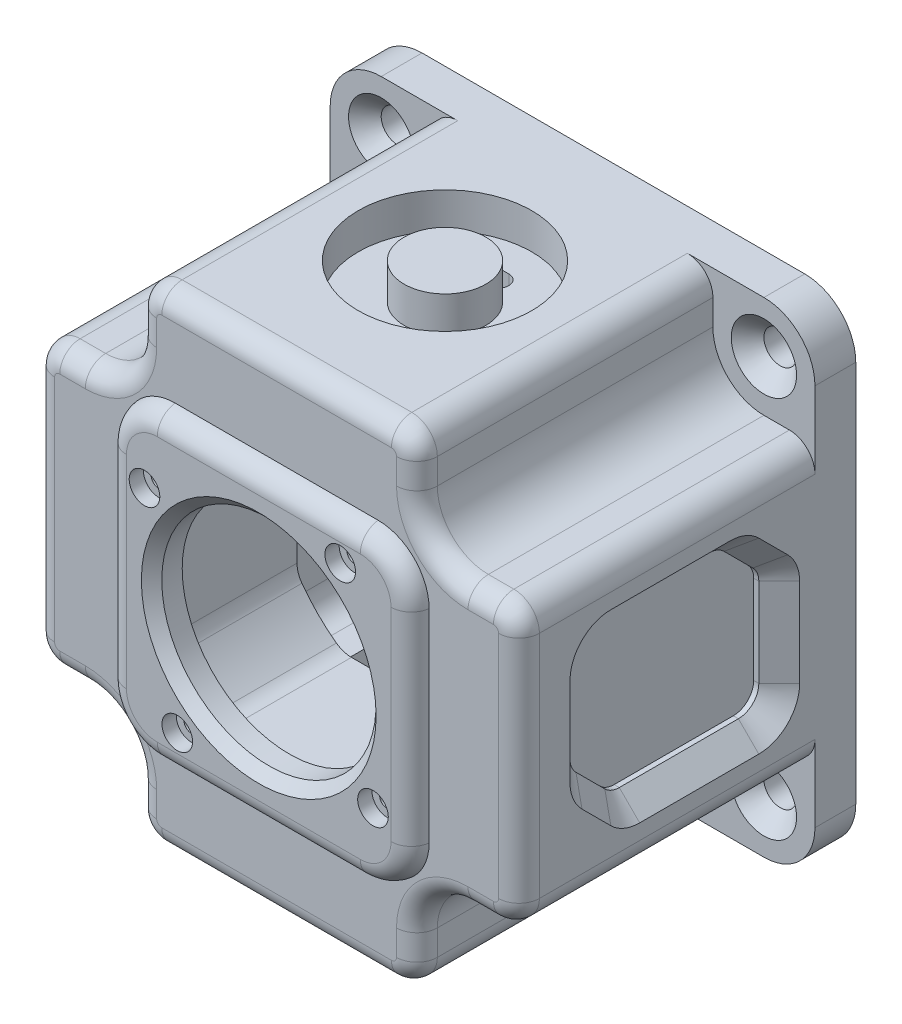
SolidWorks part; units mm, degrees
material "6061 合金"
ref_plane "前视基准面" through (0, 0, 0) normal (0, 0, 1) x (1, 0, 0)
ref_plane "上视基准面" through (0, 0, 0) normal (0, 1, 0) x (1, 0, 0)
ref_plane "右视基准面" through (0, 0, 0) normal (1, 0, 0) x (0, 0, -1)
sketch "草图1" plane through (0, 0, 0) normal (0, 0, 1) x (1, 0, 0)
  line L0 (0, 0) -> (51.7994, 0) construction
  line L1 (-37.5, 47.5) -> (37.5, 47.5)
  line L2 (-47.5, 37.5) -> (-47.5, -37.5)
  line L3 (-37.5, -47.5) -> (37.5, -47.5)
  line L4 (47.5, 37.5) -> (47.5, -37.5)
  line L5 (-47.5, 47.5) -> (47.5, -47.5) construction
  line L6 (-47.5, -47.5) -> (47.5, 47.5) construction
  line L7 (-25, 25) -> (25, 25) construction
  line L8 (-25, 25) -> (-25, -25) construction
  line L9 (-25, -25) -> (25, -25) construction
  line L10 (25, 25) -> (25, -25) construction
  line L11 (-25, 25) -> (25, -25) construction
  line L12 (-25, -25) -> (25, 25) construction
  line L13 (0, 0) -> (0, 54.2831) construction
  line L14 (-15.3297, 25) -> (15.3297, 25) construction
  line L15 (-25, 15.3297) -> (-25, -15.3297) construction
  line L16 (25, 15.3297) -> (25, -15.3297) construction
  line L17 (-15.3297, -25) -> (15.3297, -25) construction
  line L18 (26, 15.3297) -> (26, -15.3297)
  line L19 (-15.3297, -26) -> (15.3297, -26)
  line L20 (-26, 15.3297) -> (-26, -15.3297)
  line L21 (-15.3297, 26) -> (15.3297, 26)
  line L23 (37.5, -37.5) -> (-37.5, -37.5) construction
  line L24 (37.5, -37.5) -> (37.5, 37.5) construction
  line L25 (37.5, 37.5) -> (-37.5, 37.5) construction
  line L26 (-37.5, -37.5) -> (-37.5, 37.5) construction
  line L27 (37.5, -37.5) -> (-37.5, 37.5) construction
  line L28 (37.5, 37.5) -> (-37.5, -37.5) construction
  arc A1 (0, 21) -> (0, -21) centre (0, 0) ccw construction
  arc A2 (0, 21) -> (0, -21) centre (0, 0) ccw construction
  circle A3 centre (0, 0) radius 21
  arc A8 (-24.2308, 17.6881) -> (-17.6881, 24.2308) centre (0, 0) cw construction
  arc A9 (-17.4211, 24.4235) -> (-24.4235, 17.4211) centre (0, 0) ccw construction
  arc A10 (-24.2308, 17.6881) -> (-25, 15.3297) centre (-21, 15.3297) ccw construction
  arc A11 (-17.6881, 24.2308) -> (-15.3297, 25) centre (-15.3297, 21) cw construction
  arc A12 (24.2308, 17.6881) -> (25, 15.3297) centre (21, 15.3297) cw construction
  arc A13 (24.2308, 17.6881) -> (17.6881, 24.2308) centre (0, 0) ccw construction
  arc A14 (17.6881, 24.2308) -> (15.3297, 25) centre (15.3297, 21) ccw construction
  arc A15 (24.2308, -17.6881) -> (25, -15.3297) centre (21, -15.3297) ccw construction
  arc A16 (24.2308, -17.6881) -> (17.6881, -24.2308) centre (0, 0) cw construction
  arc A17 (17.6881, -24.2308) -> (15.3297, -25) centre (15.3297, -21) cw construction
  arc A18 (-17.6881, -24.2308) -> (-15.3297, -25) centre (-15.3297, -21) ccw construction
  arc A19 (-24.2308, -17.6881) -> (-17.6881, -24.2308) centre (0, 0) ccw construction
  arc A20 (-24.2308, -17.6881) -> (-25, -15.3297) centre (-21, -15.3297) cw construction
  arc A21 (25.0385, -18.2777) -> (26, -15.3297) centre (21, -15.3297) ccw
  arc A22 (25.0385, -18.2777) -> (18.2777, -25.0385) centre (0, 0) cw
  arc A23 (18.2777, -25.0385) -> (15.3297, -26) centre (15.3297, -21) cw
  arc A24 (-18.2777, -25.0385) -> (-15.3297, -26) centre (-15.3297, -21) ccw
  arc A25 (-25.0385, -18.2777) -> (-18.2777, -25.0385) centre (0, 0) ccw
  arc A26 (-25.0385, -18.2777) -> (-26, -15.3297) centre (-21, -15.3297) cw
  arc A27 (-25.0385, 18.2777) -> (-26, 15.3297) centre (-21, 15.3297) ccw
  arc A28 (-25.0385, 18.2777) -> (-18.2777, 25.0385) centre (0, 0) cw
  arc A29 (-18.2777, 25.0385) -> (-15.3297, 26) centre (-15.3297, 21) cw
  arc A30 (18.2777, 25.0385) -> (15.3297, 26) centre (15.3297, 21) ccw
  arc A31 (25.0385, 18.2777) -> (18.2777, 25.0385) centre (0, 0) ccw
  arc A32 (25.0385, 18.2777) -> (26, 15.3297) centre (21, 15.3297) cw
  arc A33 (-47.5, -37.5) -> (-37.5, -47.5) centre (-37.5, -37.5) ccw
  arc A34 (37.5, -47.5) -> (47.5, -37.5) centre (37.5, -37.5) ccw
  arc A35 (37.5, 47.5) -> (47.5, 37.5) centre (37.5, 37.5) cw
  arc A36 (-37.5, 47.5) -> (-47.5, 37.5) centre (-37.5, 37.5) ccw
  circle A37 centre (-37.5, 37.5) radius 3
  circle A40 centre (37.5, 37.5) radius 3
  circle A41 centre (37.5, -37.5) radius 3
  circle A42 centre (-37.5, -37.5) radius 3
  point P31 (-25, 16.5831)
  point P34 (-16.5831, 25)
  point P42 (0, 25)
  point P43 (25, 0)
  point P54 (-25, 0)
  dimension "D3" = 75
  dimension "D4" = 4
  dimension "D6" = 10
  dimension "D7" = 6
  dimension "D1" = 10
  dimension "D2" = 50
  dimension "D5" = 1
extrude "凸台-拉伸1" add sketch "草图1" against normal blind 60 contours L1 A36 L2 A33 L3 A34 L4 A35 A31 A32 L18 A21 A22 A23 L19 A24 A25 A26 L20 A27 A28 A29 L21 A30 region at (0, 46.1565, 0)
sketch "草图2" plane through (0, 0, 0) normal (0, 0, 1) x (1, 0, 0)
  line L0 (-47.5, 37.5) -> (-47.5, -37.5) construction
  line L1 (37.5, -47.5) -> (-37.5, -47.5)
  line L2 (47.5, -37.5) -> (47.5, 37.5)
  line L3 (37.5, 47.5) -> (-37.5, 47.5)
  line L4 (-47.5, -37.5) -> (-47.5, 37.5)
  line L5 (47.5, -47.5) -> (-47.5, 47.5) construction
  line L6 (47.5, 47.5) -> (-47.5, -47.5) construction
  line L7 (-37.5, 47.5) -> (37.5, 47.5) construction
  arc A0 (47.5, 37.5) -> (37.5, 47.5) centre (37.5, 37.5) ccw
  arc A1 (-37.5, 47.5) -> (-47.5, 37.5) centre (-37.5, 37.5) ccw
  arc A2 (-37.5, -47.5) -> (-47.5, -37.5) centre (-37.5, -37.5) cw
  arc A3 (37.5, -47.5) -> (47.5, -37.5) centre (37.5, -37.5) ccw
  circle A4 centre (37.5, -37.5) radius 10 construction
  circle A5 centre (-37.5, -37.5) radius 10 construction
  circle A6 centre (-37.5, 37.5) radius 10 construction
  circle A7 centre (37.5, 37.5) radius 10 construction
  circle A8 centre (-15.9693, -22.3882) radius 1.5
  circle A9 centre (22.3882, -15.9693) radius 1.5
  circle A10 centre (15.9693, 22.3882) radius 1.5
  circle A11 centre (-22.3882, 15.9693) radius 1.5
  circle A15 centre (-37.5, 37.5) radius 3
  circle A16 centre (37.5, 37.5) radius 3
  circle A17 centre (37.5, -37.5) radius 3
  circle A18 centre (-37.5, -37.5) radius 3
  point P0 (0, 0)
  dimension "D1" = 10
  dimension "D2" = 3
  dimension "D3" = 6
extrude "凸台-拉伸2" add sketch "草图2" along normal blind 3
sketch "草图3" plane through (0, 0, 3) normal (0, 0, 1) x (1, 0, 0)
  line L0 (27.5, -42.5) -> (27.5, -37.5)
  line L1 (-37.5, -47.5) -> (37.5, -47.5) construction
  line L2 (37.5, -27.5) -> (42.5, -27.5)
  line L3 (47.5, -37.5) -> (47.5, 37.5) construction
  line L4 (0, 0) -> (0, -50.9577) construction
  line L5 (0, 0) -> (-40.8621, 0) construction
  line L6 (47.5, 22.5) -> (47.5, -22.5)
  line L7 (22.5, -47.5) -> (-22.5, -47.5)
  line L8 (37.5, 27.5) -> (42.5, 27.5)
  line L9 (27.5, 42.5) -> (27.5, 37.5)
  line L10 (22.5, 47.5) -> (-22.5, 47.5)
  line L11 (-27.5, -42.5) -> (-27.5, -37.5)
  line L12 (-37.5, -27.5) -> (-42.5, -27.5)
  line L13 (-47.5, 22.5) -> (-47.5, -22.5)
  line L14 (-37.5, 27.5) -> (-42.5, 27.5)
  line L15 (-27.5, 42.5) -> (-27.5, 37.5)
  circle A0 centre (37.5, -37.5) radius 3 construction
  arc A1 (27.5, -37.5) -> (37.5, -27.5) centre (37.5, -37.5) cw
  arc A2 (42.5, -27.5) -> (47.5, -22.5) centre (42.5, -22.5) ccw
  arc A3 (27.5, -42.5) -> (22.5, -47.5) centre (22.5, -42.5) cw
  arc A4 (42.5, 27.5) -> (47.5, 22.5) centre (42.5, 22.5) cw
  arc A5 (27.5, 37.5) -> (37.5, 27.5) centre (37.5, 37.5) ccw
  arc A6 (27.5, 42.5) -> (22.5, 47.5) centre (22.5, 42.5) ccw
  arc A7 (-27.5, -42.5) -> (-22.5, -47.5) centre (-22.5, -42.5) ccw
  arc A8 (-27.5, -37.5) -> (-37.5, -27.5) centre (-37.5, -37.5) ccw
  arc A9 (-42.5, -27.5) -> (-47.5, -22.5) centre (-42.5, -22.5) cw
  arc A10 (-42.5, 27.5) -> (-47.5, 22.5) centre (-42.5, 22.5) ccw
  arc A11 (-27.5, 37.5) -> (-37.5, 27.5) centre (-37.5, 37.5) cw
  arc A12 (-27.5, 42.5) -> (-22.5, 47.5) centre (-22.5, 42.5) cw
  point P8 (27.5, -40)
  point P21 (47.5, -27.5)
  point P24 (27.5, -47.5)
  point P26 (47.5, 0)
  point P36 (0, -47.5)
  point P53 (0, 47.5)
  dimension "D3" = 10
  dimension "D4" = 5
  dimension "D1" = 10
  dimension "D2" = 10
extrude "凸台-拉伸3" add sketch "草图3" along normal blind 3
sketch "草图4" plane through (0, 0, 0) normal (0, 0, -1) x (-1, 0, 0)
  circle A0 centre (15.9693, -22.3882) radius 1.5 construction
  circle A1 centre (22.3882, 15.9693) radius 1.5 construction
  circle A2 centre (-15.9693, 22.3882) radius 1.5 construction
  circle A3 centre (-22.3882, -15.9693) radius 1.5 construction
  circle A4 centre (15.9693, -22.3882) radius 1.5
  circle A5 centre (22.3882, 15.9693) radius 1.5
  circle A6 centre (-15.9693, 22.3882) radius 1.5
  circle A7 centre (-22.3882, -15.9693) radius 1.5
extrude "切除-拉伸1" cut sketch "草图4" against normal through all
sketch "草图6" plane through (0, 0, 6) normal (0, 0, 1) x (1, 0, 0)
  line L12 (37.5, -27.5) -> (42.5, -27.5)
  line L13 (47.5, -22.5) -> (47.5, 22.5)
  line L14 (42.5, 27.5) -> (37.5, 27.5)
  line L15 (27.5, 37.5) -> (27.5, 42.5)
  line L16 (22.5, 47.5) -> (-22.5, 47.5)
  line L17 (-27.5, 42.5) -> (-27.5, 37.5)
  line L18 (-37.5, 27.5) -> (-42.5, 27.5)
  line L19 (-47.5, 22.5) -> (-47.5, -22.5)
  line L20 (-42.5, -27.5) -> (-37.5, -27.5)
  line L21 (-27.5, -37.5) -> (-27.5, -42.5)
  line L22 (-22.5, -47.5) -> (22.5, -47.5)
  line L23 (27.5, -42.5) -> (27.5, -37.5)
  line L24 (37.5, -27.5) -> (42.5, -27.5)
  line L25 (47.5, -22.5) -> (47.5, 22.5)
  line L26 (42.5, 27.5) -> (37.5, 27.5)
  line L27 (27.5, 37.5) -> (27.5, 42.5)
  line L28 (22.5, 47.5) -> (-22.5, 47.5)
  line L29 (-27.5, 42.5) -> (-27.5, 37.5)
  line L30 (-37.5, 27.5) -> (-42.5, 27.5)
  line L31 (-47.5, 22.5) -> (-47.5, -22.5)
  line L32 (-42.5, -27.5) -> (-37.5, -27.5)
  line L33 (-27.5, -37.5) -> (-27.5, -42.5)
  line L34 (-22.5, -47.5) -> (22.5, -47.5)
  line L35 (27.5, -42.5) -> (27.5, -37.5)
  arc A12 (37.5, -27.5) -> (27.5, -37.5) centre (37.5, -37.5) ccw
  arc A13 (42.5, -27.5) -> (47.5, -22.5) centre (42.5, -22.5) ccw
  arc A14 (47.5, 22.5) -> (42.5, 27.5) centre (42.5, 22.5) ccw
  arc A15 (27.5, 37.5) -> (37.5, 27.5) centre (37.5, 37.5) ccw
  arc A16 (27.5, 42.5) -> (22.5, 47.5) centre (22.5, 42.5) ccw
  arc A17 (-22.5, 47.5) -> (-27.5, 42.5) centre (-22.5, 42.5) ccw
  arc A18 (-37.5, 27.5) -> (-27.5, 37.5) centre (-37.5, 37.5) ccw
  arc A19 (-42.5, 27.5) -> (-47.5, 22.5) centre (-42.5, 22.5) ccw
  arc A20 (-47.5, -22.5) -> (-42.5, -27.5) centre (-42.5, -22.5) ccw
  arc A21 (-27.5, -37.5) -> (-37.5, -27.5) centre (-37.5, -37.5) ccw
  arc A22 (-27.5, -42.5) -> (-22.5, -47.5) centre (-22.5, -42.5) ccw
  arc A23 (22.5, -47.5) -> (27.5, -42.5) centre (22.5, -42.5) ccw
  arc A24 (37.5, -27.5) -> (27.5, -37.5) centre (37.5, -37.5) ccw
  arc A25 (42.5, -27.5) -> (47.5, -22.5) centre (42.5, -22.5) ccw
  arc A26 (47.5, 22.5) -> (42.5, 27.5) centre (42.5, 22.5) ccw
  arc A27 (27.5, 37.5) -> (37.5, 27.5) centre (37.5, 37.5) ccw
  arc A28 (27.5, 42.5) -> (22.5, 47.5) centre (22.5, 42.5) ccw
  arc A29 (-22.5, 47.5) -> (-27.5, 42.5) centre (-22.5, 42.5) ccw
  arc A30 (-37.5, 27.5) -> (-27.5, 37.5) centre (-37.5, 37.5) ccw
  arc A31 (-42.5, 27.5) -> (-47.5, 22.5) centre (-42.5, 22.5) ccw
  arc A32 (-47.5, -22.5) -> (-42.5, -27.5) centre (-42.5, -22.5) ccw
  arc A33 (-27.5, -37.5) -> (-37.5, -27.5) centre (-37.5, -37.5) ccw
  arc A34 (-27.5, -42.5) -> (-22.5, -47.5) centre (-22.5, -42.5) ccw
  arc A35 (22.5, -47.5) -> (27.5, -42.5) centre (22.5, -42.5) ccw
  dimension "D1" = 0
extrude "切除-拉伸2" cut sketch "草图6" against normal blind 58 flip side to cut contours A24 L35 A35 L34 A34 L33 A33 L32 A32 L31 A31 L30 A30 L29 A29 L28 A28 L27 A27 L26 A26 L25 A25 L24
sketch "草图9" plane through (0, 0, 6) normal (0, 0, 1) x (1, 0, 0)
  line L1 (-19.8882, -29.8882) -> (19.8882, -29.8882)
  line L2 (-29.8882, -19.8882) -> (-29.8882, 19.8882)
  line L3 (-19.8882, 29.8882) -> (19.8882, 29.8882)
  line L4 (29.8882, -19.8882) -> (29.8882, 19.8882)
  line L5 (-29.8882, -29.8882) -> (29.8882, 29.8882) construction
  line L6 (-29.8882, 29.8882) -> (29.8882, -29.8882) construction
  arc A0 (-29.8882, 19.8882) -> (-19.8882, 29.8882) centre (-19.8882, 19.8882) cw
  arc A1 (-19.8882, -29.8882) -> (-29.8882, -19.8882) centre (-19.8882, -19.8882) cw
  arc A2 (19.8882, 29.8882) -> (29.8882, 19.8882) centre (19.8882, 19.8882) cw
  arc A3 (19.8882, -29.8882) -> (29.8882, -19.8882) centre (19.8882, -19.8882) ccw
  circle A4 centre (-22.3882, 15.9693) radius 1.5
  circle A5 centre (15.9693, 22.3882) radius 1.5
  circle A6 centre (22.3882, -15.9693) radius 1.5
  circle A7 centre (-15.9693, -22.3882) radius 1.5
  point P0 (0, 0)
  dimension "D2" = 10
  dimension "D3" = 3
  dimension "D1" = 7.5
extrude "凸台-拉伸4" add sketch "草图9" along normal blind 3.5
fillet "圆角1" radius 4 8 edges at (-26.9592, 26.9592, 9.5) (0, 29.8882, 9.5) (26.9592, 26.9592, 9.5) (29.8882, 0, 9.5) (26.9592, -26.9592, 9.5) (0, -29.8882, 9.5) (-26.9592, -26.9592, 9.5) (-29.8882, 0, 9.5)
sketch "草图7" plane through (0, 0, 9.5) normal (0, 0, 1) x (1, 0, 0)
  circle A0 centre (0, 0) radius 21
  dimension "D1" = 42
extrude "切除-拉伸3" cut sketch "草图7" against normal through all
sketch "草图8" plane through (0, 0, 9.5) normal (0, 0, 1) x (1, 0, 0)
  circle A0 centre (-15.9693, -22.3882) radius 3
  circle A1 centre (-22.3882, 15.9693) radius 3
  circle A2 centre (15.9693, 22.3882) radius 3
  circle A3 centre (22.3882, -15.9693) radius 3
  dimension "D1" = 6
extrude "切除-拉伸4" cut sketch "草图8" against normal blind 2.8
fillet "圆角2" radius 4 24 edges at (-40, -27.5, 6) (-46.0355, -26.0355, 6) (-47.5, 0, 6) (-46.0355, 26.0355, 6) (-40, 27.5, 6) (-30.4289, 30.4289, 6) (-27.5, 40, 6) (-26.0355, 46.0355, 6) (0, 47.5, 6) (26.0355, 46.0355, 6) (27.5, 40, 6) (30.4289, 30.4289, 6) (40, 27.5, 6) (46.0355, 26.0355, 6) (47.5, 0, 6) (46.0355, -26.0355, 6) (40, -27.5, 6) (30.4289, -30.4289, 6) (27.5, -40, 6) (26.0355, -46.0355, 6) (0, -47.5, 6) (-26.0355, -46.0355, 6) (-27.5, -40, 6) (-30.4289, -30.4289, 6)
sketch "草图10" plane through (47.5, 0, 0) normal (1, 0, 0) x (0, 0, -1)
  line L0 (17.6569, -15.5) -> (41, -15.5)
  line L1 (45, -11.5) -> (45, 5.8431)
  line L2 (43.8284, 8.6716) -> (38.1716, 14.3284)
  line L3 (35.3431, 15.5) -> (12, 15.5)
  line L4 (8, 11.5) -> (8, -5.8431)
  line L5 (9.1716, -8.6716) -> (14.8284, -14.3284)
  line L6 (-6, -22.5) -> (-6, 22.5) construction
  line L7 (60, 37.5) -> (60, -37.5) construction
  line L8 (-2, -22.5) -> (52, -22.5) construction
  line L9 (-2, 22.5) -> (52, 22.5) construction
  arc A0 (41, -15.5) -> (45, -11.5) centre (41, -11.5) ccw
  arc A1 (45, 5.8431) -> (43.8284, 8.6716) centre (41, 5.8431) ccw
  arc A2 (38.1716, 14.3284) -> (35.3431, 15.5) centre (35.3431, 11.5) ccw
  arc A3 (12, 15.5) -> (8, 11.5) centre (12, 11.5) ccw
  arc A4 (8, -5.8431) -> (9.1716, -8.6716) centre (12, -5.8431) ccw
  arc A5 (17.6569, -15.5) -> (14.8284, -14.3284) centre (17.6569, -11.5) cw
  point P18 (45, 7.5)
  dimension "D7" = 4
  dimension "D1" = 135
  dimension "D2" = 14
  dimension "D3" = 15
  dimension "D4" = 7
  dimension "D5" = 7
  dimension "D6" = 15
extrude "切除-拉伸5" cut sketch "草图10" against normal blind 5
chamfer "倒角1" distance 4 angle 45 12 edges at (47.5, -2.8284, -45) (47.5, 7.3739, -44.6955) (47.5, -14.3284, -43.8284) (47.5, 11.5, -41) (47.5, -15.5, -29.3284) (47.5, 15.1955, -36.8739) (47.5, -15.1955, -16.1261) (47.5, 15.5, -23.6716) (47.5, -11.5, -12) (47.5, 14.3284, -9.1716) (47.5, -7.3739, -8.3045) (47.5, 2.8284, -8)
chamfer "倒角2" distance 2 angle 45 1 edges at (21, 0, 9.5)
sketch "草图11" plane through (-47.5, 0, 0) normal (-1, 0, 0) x (0, 0, 1)
  line L10 (-9.1716, -8.6716) -> (-14.8284, -14.3284)
  line L11 (-17.6569, -15.5) -> (-41, -15.5)
  line L12 (-45, -11.5) -> (-45, 5.8431)
  line L13 (-43.8284, 8.6716) -> (-38.1716, 14.3284)
  line L14 (-35.3431, 15.5) -> (-12, 15.5)
  line L15 (-8, 11.5) -> (-8, -5.8431)
  line L16 (6, 19.8882) -> (6, -19.8882) construction
  line L17 (-60, 37.5) -> (-60, -37.5) construction
  line L18 (2, -22.5) -> (-52, -22.5) construction
  line L19 (2, 22.5) -> (-52, 22.5) construction
  arc A6 (-9.1716, -8.6716) -> (-8, -5.8431) centre (-12, -5.8431) ccw
  arc A7 (-14.8284, -14.3284) -> (-17.6569, -15.5) centre (-17.6569, -11.5) cw
  arc A8 (-41, -15.5) -> (-45, -11.5) centre (-41, -11.5) cw
  arc A9 (-45, 5.8431) -> (-43.8284, 8.6716) centre (-41, 5.8431) cw
  arc A10 (-38.1716, 14.3284) -> (-35.3431, 15.5) centre (-35.3431, 11.5) cw
  arc A11 (-12, 15.5) -> (-8, 11.5) centre (-12, 11.5) cw
  point P22 (-45, 7.5)
  dimension "D7" = 4
  dimension "D1" = 14
  dimension "D2" = 15
  dimension "D3" = 7
  dimension "D4" = 7
  dimension "D5" = 15
  dimension "D6" = 135
extrude "切除-拉伸6" cut sketch "草图11" against normal blind 5
chamfer "倒角3" distance 4 angle 45 12 edges at (-47.5, -2.8284, -45) (-47.5, -14.3284, -43.8284) (-47.5, 7.3739, -44.6955) (-47.5, -15.5, -29.3284) (-47.5, 11.5, -41) (-47.5, -15.1955, -16.1261) (-47.5, 15.1955, -36.8739) (-47.5, -11.5, -12) (-47.5, 15.5, -23.6716) (-47.5, -7.3739, -8.3045) (-47.5, 14.3284, -9.1716) (-47.5, 2.8284, -8)
sketch "草图12" plane through (0, 47.5, 0) normal (0, 1, 0) x (1, 0, 0)
  line L1 (22.5, 56) -> (-22.5, 56) construction
  line L2 (22.5, 56) -> (22.5, -2) construction
  line L3 (22.5, -2) -> (-22.5, -2) construction
  line L4 (-22.5, 56) -> (-22.5, -2) construction
  line L5 (22.5, 56) -> (-22.5, -2) construction
  line L6 (22.5, -2) -> (-22.5, 56) construction
  line L7 (-37.5, 60) -> (37.5, 60) construction
  line L8 (22.5, -2) -> (22.5, 52) construction
  circle A0 centre (0, 27) radius 8
  circle A1 centre (0, 27) radius 17
  dimension "D2" = 16
  dimension "D3" = 34
  dimension "D1" = 4
extrude "切除-拉伸7" cut sketch "草图12" against normal blind 7
sketch "草图13" plane through (0, 40.5, 0) normal (0, 1, 0) x (1, 0, 0)
  line L0 (1.5, 36) -> (-1.5, 36) construction
  line L1 (1.5, 34) -> (-1.5, 34)
  line L2 (1.5, 38) -> (-1.5, 38)
  line L3 (0, 36) -> (0, 0) construction
  arc A0 (1.5, 34) -> (1.5, 38) centre (1.5, 36) ccw
  arc A1 (-1.5, 38) -> (-1.5, 34) centre (-1.5, 36) ccw
  point P2 (0, 36)
  dimension "D1" = 4
  dimension "D2" = 3
  dimension "D3" = 36
extrude "切除-拉伸8" cut sketch "草图13" against normal blind 23
hole_wizard "打孔尺寸(%根据)内六角花形半沉头螺钉的类型1" positions "草图16" profile "草图15" countersink size "M6" standard "GB"
sketch "草图16" plane through (0, 0, -52) normal (0, 0, 1) x (1, 0, 0)
  point P0 (-37.5, -37.5)
  point P3 (37.5, -37.5)
  point P6 (37.5, 37.5)
  point P9 (-37.5, 37.5)
sketch "草图15" plane through (-37.5, -37.5, -52) normal (1, 0, 0) x (0, -1, 0)
  line L0 (0, 0) -> (0, 10.0228)
  line L1 (0, 10.0228) -> (3.2, 8.1)
  line L2 (3.2, 8.1) -> (3.2, 3.2)
  line L3 (3.2, 3.2) -> (6.4, 0)
  line L5 (6.4, 0) -> (0, 0)
  line L6 (-3.2, 3.2) -> (-6.4, 0) construction
  line L10 (0, 10.0228) -> (-3.2, 8.1) construction
  line L11 (0, -6.35) -> (0, 107.95) construction
  dimension "孔直径" = 6.4
  dimension "孔深度" = 8.1
  dimension "近端锥形沉头孔直径" = 12.8
  dimension "近端锥形沉头孔角度" = 90
  dimension "导头角度" = 118
sketch "草图17" plane through (0, -47.5, 0) normal (0, -1, 0) x (1, 0, 0)
  line L0 (22.5, 2) -> (-22.5, 2) construction
  line L1 (-15.5, -4) -> (15.5, -4)
  line L2 (-19.5, -8) -> (-19.5, -43)
  line L3 (-15.5, -47) -> (15.5, -47)
  line L4 (19.5, -8) -> (19.5, -43)
  line L5 (-19.5, -4) -> (19.5, -47) construction
  line L6 (-19.5, -47) -> (19.5, -4) construction
  line L7 (-22.5, -52) -> (-37.5, -52) construction
  line L8 (-22.5, 2) -> (-22.5, -52) construction
  line L9 (22.5, 2) -> (22.5, -52) construction
  arc A0 (15.5, -47) -> (19.5, -43) centre (15.5, -43) ccw
  arc A1 (15.5, -4) -> (19.5, -8) centre (15.5, -8) cw
  arc A2 (-19.5, -43) -> (-15.5, -47) centre (-15.5, -43) ccw
  arc A3 (-15.5, -4) -> (-19.5, -8) centre (-15.5, -8) ccw
  point P0 (0, -25.5)
  dimension "D5" = 4
  dimension "D1" = 6
  dimension "D2" = 5
  dimension "D3" = 3
  dimension "D4" = 3
extrude "切除-拉伸9" cut sketch "草图17" against normal blind 17.5
sketch "草图18" plane through (0, 0, -60) normal (0, 0, -1) x (-1, 0, 0)
  line L1 (-25, 30) -> (25, 30)
  line L2 (-30, 25) -> (-30, -25)
  line L3 (-25, -30) -> (25, -30)
  line L4 (30, 25) -> (30, -25)
  line L5 (-30, 30) -> (30, -30) construction
  line L6 (-30, -30) -> (30, 30) construction
  arc A0 (25, -30) -> (30, -25) centre (25, -25) ccw
  arc A1 (25, 30) -> (30, 25) centre (25, 25) cw
  arc A2 (-30, -25) -> (-25, -30) centre (-25, -25) ccw
  arc A3 (-25, 30) -> (-30, 25) centre (-25, 25) ccw
  point P0 (0, 0)
  dimension "D1" = 5
  dimension "D2" = 60
extrude "切除-拉伸10" cut sketch "草图18" against normal offset from surface (36 mm away) 20 up to face at (0, -38.75, -4)
sketch "草图19" plane through (0, 0, 0) normal (0, 0, -1) x (-1, 0, 0)
  line L4 (-26, 15.3297) -> (-26, -15.3297)
  line L5 (-15.3297, -26) -> (15.3297, -26)
  line L6 (26, -15.3297) -> (26, 15.3297)
  line L7 (15.3297, 26) -> (-15.3297, 26)
  line L8 (-26, 15.3297) -> (-26, -15.3297)
  line L9 (-15.3297, -26) -> (15.3297, -26)
  line L10 (26, -15.3297) -> (26, 15.3297)
  line L11 (15.3297, 26) -> (-15.3297, 26)
  circle A0 centre (-15.9693, 22.3882) radius 1.5
  circle A1 centre (22.3882, 15.9693) radius 1.5
  circle A2 centre (-22.3882, -15.9693) radius 1.5
  circle A3 centre (15.9693, -22.3882) radius 1.5
  arc A12 (-18.2777, 25.0385) -> (-25.0385, 18.2777) centre (0, 0) ccw
  arc A13 (-25.0385, 18.2777) -> (-26, 15.3297) centre (-21, 15.3297) ccw
  arc A14 (-26, -15.3297) -> (-25.0385, -18.2777) centre (-21, -15.3297) ccw
  arc A15 (-25.0385, -18.2777) -> (-18.2777, -25.0385) centre (0, 0) ccw
  arc A16 (-18.2777, -25.0385) -> (-15.3297, -26) centre (-15.3297, -21) ccw
  arc A17 (15.3297, -26) -> (18.2777, -25.0385) centre (15.3297, -21) ccw
  arc A18 (18.2777, -25.0385) -> (25.0385, -18.2777) centre (0, 0) ccw
  arc A19 (25.0385, -18.2777) -> (26, -15.3297) centre (21, -15.3297) ccw
  arc A20 (26, 15.3297) -> (25.0385, 18.2777) centre (21, 15.3297) ccw
  arc A21 (25.0385, 18.2777) -> (18.2777, 25.0385) centre (0, 0) ccw
  arc A22 (18.2777, 25.0385) -> (15.3297, 26) centre (15.3297, 21) ccw
  arc A23 (-15.3297, 26) -> (-18.2777, 25.0385) centre (-15.3297, 21) ccw
  arc A24 (-18.2777, 25.0385) -> (-25.0385, 18.2777) centre (0, 0) ccw
  arc A25 (-25.0385, 18.2777) -> (-26, 15.3297) centre (-21, 15.3297) ccw
  arc A26 (-26, -15.3297) -> (-25.0385, -18.2777) centre (-21, -15.3297) ccw
  arc A27 (-25.0385, -18.2777) -> (-18.2777, -25.0385) centre (0, 0) ccw
  arc A28 (-18.2777, -25.0385) -> (-15.3297, -26) centre (-15.3297, -21) ccw
  arc A29 (15.3297, -26) -> (18.2777, -25.0385) centre (15.3297, -21) ccw
  arc A30 (18.2777, -25.0385) -> (25.0385, -18.2777) centre (0, 0) ccw
  arc A31 (25.0385, -18.2777) -> (26, -15.3297) centre (21, -15.3297) ccw
  arc A32 (26, 15.3297) -> (25.0385, 18.2777) centre (21, 15.3297) ccw
  arc A33 (25.0385, 18.2777) -> (18.2777, 25.0385) centre (0, 0) ccw
  arc A34 (18.2777, 25.0385) -> (15.3297, 26) centre (15.3297, 21) ccw
  arc A35 (-15.3297, 26) -> (-18.2777, 25.0385) centre (-15.3297, 21) ccw
  dimension "D1" = 0
extrude "切除-拉伸11" cut sketch "草图19" against normal blind 3.5
sketch "草图20" plane through (0, 0, -60) normal (0, 0, -1) x (-1, 0, 0)
  line L0 (30, -25) -> (30, 25) construction
  line L1 (33, 12) -> (-33, 12)
  line L2 (35, 10) -> (35, -10)
  line L3 (33, -12) -> (-33, -12)
  line L4 (-35, 10) -> (-35, -10)
  line L5 (35, 12) -> (-35, -12) construction
  line L6 (35, -12) -> (-35, 12) construction
  arc A0 (-33, 12) -> (-35, 10) centre (-33, 10) ccw
  arc A1 (-33, -12) -> (-35, -10) centre (-33, -10) cw
  arc A2 (35, -10) -> (33, -12) centre (33, -10) cw
  arc A3 (33, 12) -> (35, 10) centre (33, 10) cw
  point P0 (0, 0)
  dimension "D3" = 2
  dimension "D1" = 5
  dimension "D2" = 24
extrude "切除-拉伸12" cut sketch "草图20" against normal up to surface (36 mm away) up to face at (0, -6, -24)
fillet "圆角3" radius 2 4 edges at (-30, -12, -42) (-30, 12, -42) (30, -12, -42) (30, 12, -42)
